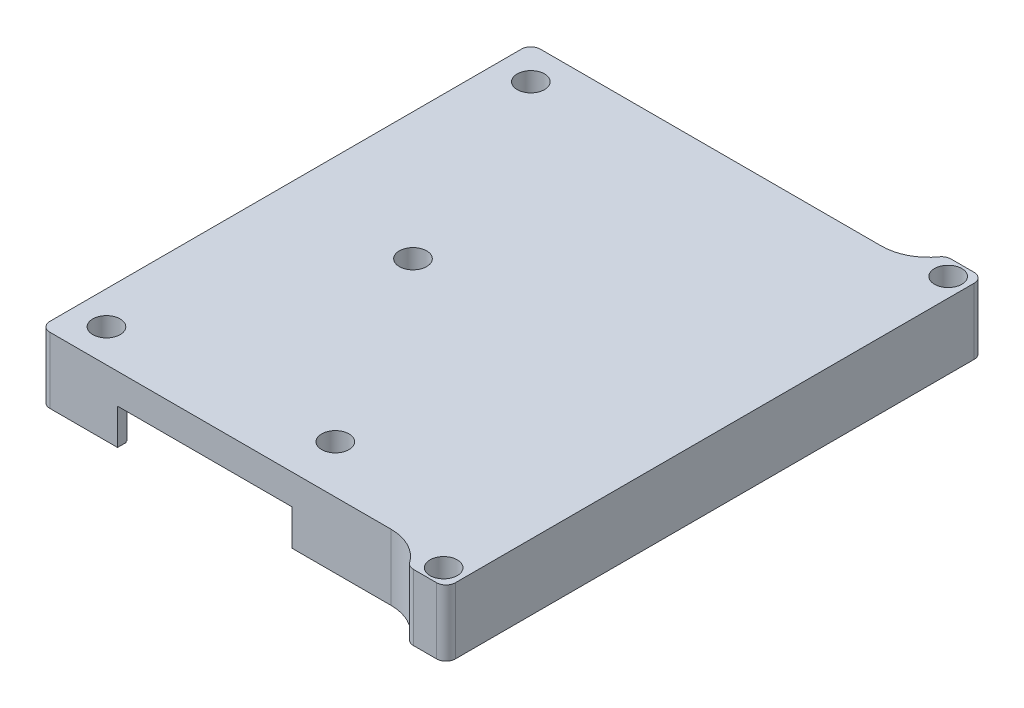
SolidWorks part; units mm, degrees
ref_plane "Front Plane" through (0, 0, 0) normal (0, 0, 1) x (1, 0, 0)
ref_plane "Top Plane" through (0, 0, 0) normal (0, 1, 0) x (1, 0, 0)
ref_plane "Right Plane" through (0, 0, 0) normal (1, 0, 0) x (0, 0, -1)
sketch "Sketch1" plane through (0, 0, 0) normal (0, 1, 0) x (1, 0, 0)
  line L0 (89, -2) -> (89, 102)
  line L1 (0, 0) -> (87, 0)
  line L2 (0, 0) -> (0, 100)
  line L3 (0, 100) -> (87, 100)
  line L4 (87, 0) -> (87, 100)
  line L5 (-2, 102) -> (89, 102)
  line L6 (-2, -2) -> (-2, 102)
  line L7 (-2, -2) -> (89, -2)
  dimension "D1" = 100
  dimension "D2" = 87
  dimension "D3" = 2
extrude "Boss-Extrude1" add sketch "Sketch1" against normal blind 12
sketch "Sketch2" plane through (0, 0, 0) normal (0, 1, 0) x (1, 0, 0)
  line L1 (-2, 102) -> (89, 102)
  line L2 (-2, 102) -> (-2, -2)
  line L3 (-2, -2) -> (89, -2)
  line L4 (89, 102) -> (89, -2)
extrude "Boss-Extrude2" add sketch "Sketch2" along normal blind 2
sketch "Sketch3" plane through (0, 0, 0) normal (0, -1, 0) x (1, 0, 0)
  circle A0 centre (5, -5) radius 3.5
  circle A1 centre (5, -95) radius 3.5
  circle A4 centre (50.38, -8.15) radius 3.5
  circle A5 centre (25, -50) radius 3.5
  dimension "D9" = 7
  dimension "D1" = 5
  dimension "D2" = 5
  dimension "D3" = 8.15
  dimension "D5" = 50.38
  dimension "D6" = 25
  dimension "D7" = 50
  dimension "D8" = 95
extrude "Boss-Extrude3" add sketch "Sketch3" along normal up to surface (12 mm away) up to face at (43.5, -12, -50)
sketch "Sketch6" plane through (0, 2, 0) normal (0, 1, 0) x (1, 0, 0)
  line L0 (89, 102) -> (-2, 102) construction
  line L1 (81, 102) -> (89, 102)
  line L2 (81, 102) -> (81, 107)
  line L3 (81, 107) -> (89, 107)
  line L4 (89, 102) -> (89, 107)
  line L6 (89, -2) -> (81, -2)
  line L7 (89, -2) -> (89, -7)
  line L8 (89, -7) -> (81, -7)
  line L9 (81, -2) -> (81, -7)
  dimension "D1" = 5
  dimension "D2" = 8
extrude "Boss-Extrude4" add sketch "Sketch6" against normal through all
sketch "Sketch4" plane through (0, 2, 0) normal (0, 1, 0) x (1, 0, 0)
  line L0 (89, -7) -> (89, 107) construction
  line L3 (81, 102) -> (-2, 102) construction
  line L4 (-2, -2) -> (81, -2) construction
  circle A0 centre (5, 5) radius 1.5
  circle A1 centre (5, 95) radius 1.5
  circle A2 centre (50.38, 8.15) radius 1.5
  circle A3 centre (25, 50) radius 1.5
  circle A4 centre (85, 103.5) radius 1.5
  circle A5 centre (85, -3.5) radius 1.5
  dimension "D1" = 3
  dimension "D2" = 4
  dimension "D4" = 1.5
  dimension "D3" = 1.5
extrude "Cut-Extrude1" cut sketch "Sketch4" against normal up to next
sketch "Sketch7" plane through (0, 2, 0) normal (0, 1, 0) x (1, 0, 0)
  circle A0 centre (5, 5) radius 2.9
  circle A1 centre (25, 50) radius 2.9
  circle A2 centre (50.38, 8.15) radius 2.9
  circle A3 centre (5, 95) radius 2.9
  circle A4 centre (85, 103.5) radius 2.9
  circle A5 centre (85, -3.5) radius 2.9
  dimension "D1" = 5.8
extrude "Cut-Extrude2" cut sketch "Sketch7" against normal offset from surface (8 mm away) 6 up to face at (5, -12, -3.5)
sketch "Sketch8" plane through (0, 0, -100) normal (0, 0, 1) x (1, 0, 0)
  line L0 (87, -12) -> (0, -12) construction
  line L1 (83, -12) -> (50, -12)
  line L2 (83, -12) -> (83, -10)
  line L3 (83, -10) -> (50, -10)
  line L4 (50, -12) -> (50, -10)
  line L5 (87, -12) -> (87, 0) construction
  dimension "D1" = 2
  dimension "D2" = 4
  dimension "D3" = 33
extrude "Cut-Extrude3" cut sketch "Sketch8" against normal blind 1.3
sketch "Sketch9" plane through (0, -12, 0) normal (0, -1, 0) x (-1, 0, 0)
  line L0 (0.2, -0.2) -> (0.2, 100.2)
  line L1 (0, 0) -> (-87, 0)
  line L2 (0, 0) -> (0, 100)
  line L3 (0, 100) -> (-87, 100)
  line L4 (-87, 0) -> (-87, 100)
  line L5 (0.2, 100.2) -> (-87.2, 100.2)
  line L6 (-87.2, -0.2) -> (-87.2, 100.2)
  line L7 (0.2, -0.2) -> (-87.2, -0.2)
  dimension "D1" = 0.2
extrude "Cut-Extrude4" cut sketch "Sketch9" against normal blind 0.2
sketch "Sketch10" plane through (0, 0, -100) normal (0, 0, 1) x (1, 0, 0)
  line L0 (87, 0) -> (0, 0) construction
  line L1 (50, -10) -> (56, -10)
  line L2 (50, -10) -> (50, 0)
  line L3 (50, 0) -> (56, 0)
  line L4 (56, -10) -> (56, 0)
  line L5 (83, -10) -> (50, -10) construction
  line L6 (83, -10) -> (77, -10)
  line L7 (83, -10) -> (83, 0)
  line L8 (83, 0) -> (77, 0)
  line L9 (77, -10) -> (77, 0)
  dimension "D1" = 6
extrude "Boss-Extrude7" add sketch "Sketch10" along normal blind 5
sketch "Sketch11" plane through (0, 0, -102) normal (0, 0, -1) x (-1, 0, 0)
  line L0 (-81, -12) -> (2, -12) construction
  line L10 (-41.957, -12) -> (-31.457, -12)
  line L11 (-41.957, -12) -> (-41.957, -9)
  line L12 (-40.957, -8) -> (-32.457, -8)
  line L13 (-31.457, -12) -> (-31.457, -9)
  circle A0 centre (-43.257, -10.5) radius 0.75
  arc A1 (-32.457, -8) -> (-31.457, -9) centre (-32.457, -9) cw
  arc A2 (-41.957, -9) -> (-40.957, -8) centre (-40.957, -9) cw
  point P3 (-41.957, -10.5)
  point P12 (-36.707, -8)
  point P16 (-31.457, -8)
  point P19 (-41.957, -8)
  dimension "D1" = 1.5
  dimension "D6" = 1
  dimension "D2" = 4
  dimension "D3" = 6.55
  dimension "D4" = 10.5
  dimension "D5" = 36.707
extrude "Cut-Extrude5" cut sketch "Sketch11" against normal up to next
sketch "Sketch12" plane through (0, 0, 2) normal (0, 0, 1) x (1, 0, 0)
  line L0 (-2, -12) -> (81, -12) construction
  line L1 (14.35, -12) -> (51.35, -12)
  line L2 (14.35, -12) -> (14.35, -4.4)
  line L3 (14.35, -4.4) -> (51.35, -4.4)
  line L4 (51.35, -12) -> (51.35, -4.4)
  dimension "D1" = 37
  dimension "D2" = 7.6
  dimension "D3" = 14.35
extrude "Cut-Extrude6" cut sketch "Sketch12" against normal blind 7
sketch "Sketch13" plane through (-2, 0, 0) normal (-1, 0, 0) x (0, 0, 1)
  line L0 (-102, -12) -> (2, -12) construction
  line L1 (-86, -12) -> (-14, -12)
  line L2 (-86, -12) -> (-86, -4.4)
  line L3 (-86, -4.4) -> (-14, -4.4)
  line L4 (-14, -12) -> (-14, -4.4)
  line L5 (2, -4.4) -> (2, -12) construction
  dimension "D1" = 72
  dimension "D2" = 14
extrude "Cut-Extrude7" cut sketch "Sketch13" against normal up to next
fillet "Fillet1" radius 10 2 edges at (81, -5, -102) (81, -5, 2)
fillet "Fillet2" radius 2 6 edges at (-2, -5, 2) (-2, -5, -102) (81, -5, -107) (89, -5, -107) (89, -5, 7) (81, -5, 7)
sketch "Sketch14" plane through (0, 0, -100) normal (0, 0, 1) x (1, 0, 0)
  line L1 (26.757, -12) -> (16.757, -12)
  line L2 (26.757, -12) -> (26.757, -8)
  line L3 (26.757, -8) -> (16.757, -8)
  line L4 (16.757, -12) -> (16.757, -8)
  line L5 (-0.2, -12) -> (31.457, -12) construction
  line L6 (31.457, -9) -> (31.457, -11.8) construction
  point P4 (0, 0)
  dimension "D1" = 4.7
  dimension "D2" = 10
  dimension "D3" = 4
extrude "Cut-Extrude8" cut sketch "Sketch14" against normal blind 0.5
equation "\"D4@Sketch4\"=\"D3@Sketch4\""
